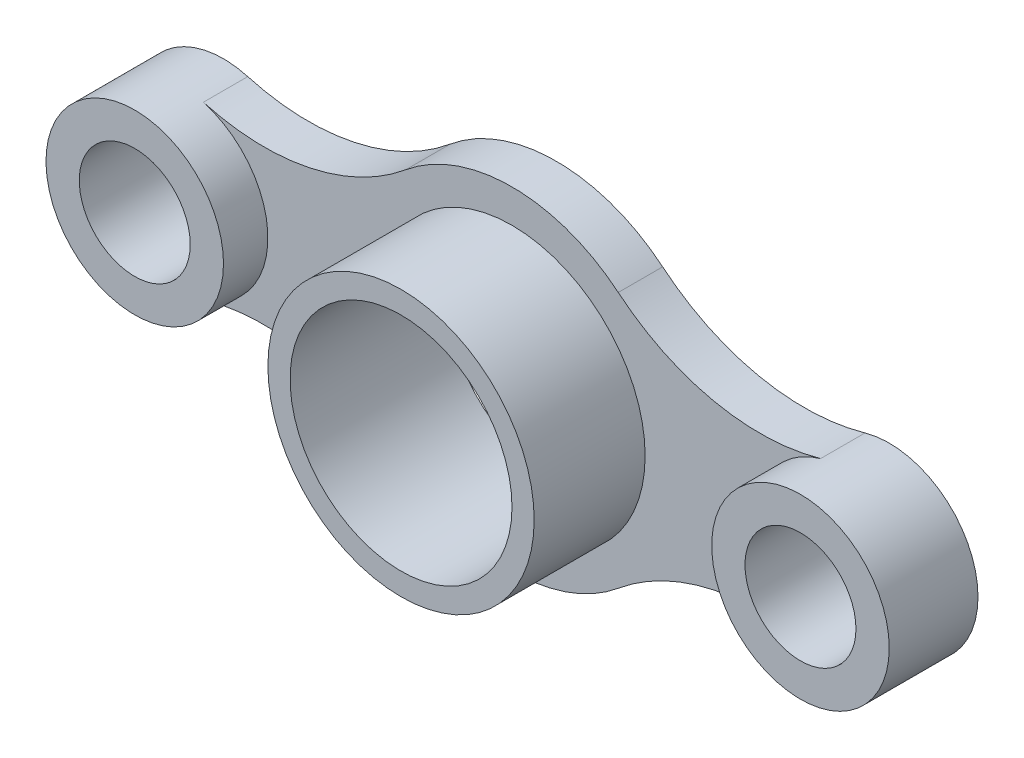
SolidWorks part; units mm, degrees
ref_plane "Front Plane" through (0, 0, 0) normal (0, 0, 1) x (1, 0, 0)
ref_plane "Top Plane" through (0, 0, 0) normal (0, 1, 0) x (1, 0, 0)
ref_plane "Right Plane" through (0, 0, 0) normal (1, 0, 0) x (0, 0, -1)
sketch "Sketch2" plane through (0, 0, 0) normal (0, 0, 1) x (1, 0, 0)
  line L0 (-332.0896, 0) -> (406.7164, 0) construction
  line L1 (0, 266.791) -> (0, -249.6269) construction
  line L2 (150, 247.3881) -> (150, -239.1791) construction
  line L4 (-150, -239.1791) -> (-150, 266.791) construction
  circle A0 centre (0, 0) radius 60
  circle A1 centre (0, 0) radius 50
  arc A2 (-47.8929, -57.7172) -> (47.8929, -57.7172) centre (0, 0) ccw
  circle A3 centre (-150, 0) radius 25
  circle A4 centre (-150, 0) radius 40
  circle A5 centre (150, 0) radius 25
  circle A6 centre (150, 0) radius 40
  arc A7 (-47.8929, -57.7172) -> (-139.0714, -38.4781) centre (-111.75, -134.6734) ccw
  arc A8 (-139.0714, 38.4781) -> (-47.8929, 57.7172) centre (-111.75, 134.6734) ccw
  arc A9 (47.8929, -57.7172) -> (139.0714, -38.4781) centre (111.75, -134.6734) cw
  arc A10 (139.0714, 38.4781) -> (47.8929, 57.7172) centre (111.75, 134.6734) cw
  arc A11 (47.8929, 57.7172) -> (-47.8929, 57.7172) centre (0, 0) ccw
  point P27 (-113.4328, 136.194)
  point P28 (-111.75, -164.2386)
  dimension "D3" = 120
  dimension "D4" = 100
  dimension "D5" = 150
  dimension "D6" = 80
  dimension "D7" = 50
  dimension "D1" = 150
  dimension "D2" = 150
extrude "Boss-Extrude1" add sketch "Sketch2" along normal blind 20 contours A10 A11 A8 A4 A7 A2 A9 A6 A0 region at (-90.4517, -33.7359, 0)
extrude "Boss-Extrude4" add sketch "Sketch2<5>" along normal blind 40 contours A4 A3 | A6 A5 region at (-188.8686, 0, 0) region at (111.1314, 0, 0)
sketch "Sketch2<5>" plane through (0, 0, 0) normal (0, 0, 1) x (1, 0, 0) same geometry as "Sketch2"
extrude "Boss-Extrude5" add sketch "Sketch2<6>" along normal blind 70 contours A0 A1 region at (-58.3029, 0, 0)
sketch "Sketch2<6>" plane through (0, 0, 0) normal (0, 0, 1) x (1, 0, 0) same geometry as "Sketch2"
